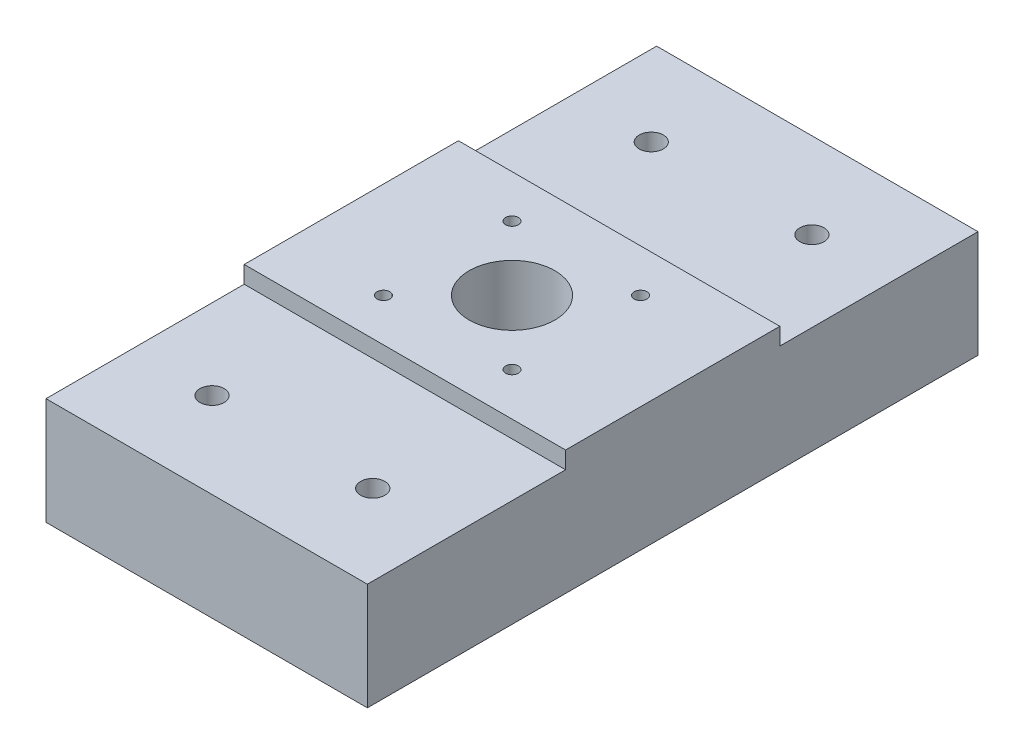
SolidWorks part; units mm, degrees
ref_plane "Front Plane" through (0, 0, 0) normal (0, 0, 1) x (1, 0, 0)
ref_plane "Top Plane" through (0, 0, 0) normal (0, 1, 0) x (1, 0, 0)
ref_plane "Right Plane" through (0, 0, 0) normal (1, 0, 0) x (0, 0, -1)
sketch "Sketch1" plane through (0, 0, 0) normal (0, 1, 0) x (1, 0, 0)
  line L0 (9, -22.5) -> (21, -22.5) construction
  line L1 (0, 0) -> (30, 0)
  line L2 (0, 0) -> (0, -57)
  line L3 (0, -57) -> (30, -57)
  line L4 (30, 0) -> (30, -57)
  line L5 (0, -18.5) -> (30, -18.5)
  line L6 (0, -18.5) -> (0, -38.5)
  line L7 (0, -38.5) -> (30, -38.5)
  line L8 (30, -18.5) -> (30, -38.5)
  line L9 (21, -22.5) -> (21, -34.5) construction
  line L10 (21, -34.5) -> (9, -34.5) construction
  line L11 (9, -34.5) -> (9, -22.5) construction
  circle A0 centre (15, -28.5) radius 4
  point P11 (15, 0)
  point P12 (22.5, -49)
  point P13 (9, -22.5)
  point P14 (21, -34.5)
  point P15 (9, -34.5)
  point P16 (7.5, -8)
  point P17 (22.5, -8)
  point P20 (8.5074, -34.6341)
  point P21 (7.5, -49)
  point P22 (15, -22.5)
  point P23 (21, -22.5)
  point P24 (21, -28.5)
  dimension "D3" = 8
  dimension "D1" = 57
  dimension "D2" = 30
  dimension "D4" = 10
  dimension "D5" = 20
  dimension "D6" = 15
  dimension "D7" = 7.5
  dimension "D8" = 18.5
  dimension "D9" = 8
  dimension "D10" = 8
  dimension "D11" = 12
extrude "Main_Body" add sketch "Sketch1" along normal blind 10 contours L7 L2 L3 L4 | L2 L7 L4 L5 A0 | L2 L5 L4 L1 region at (15, 0, 9.25) region at (15, 0, 18.8606) region at (15, 0, 47.75)
extrude "Boss-Extrude2" add sketch "Sketch1<3>" along normal blind 1.6 from surface contours L2 L7 L4 L5 A0 region at (15, 0, 18.8606) starting at face at (15, 10, 28.5)
sketch "Sketch1<3>" plane through (0, 0, 0) normal (0, 1, 0) x (1, 0, 0) same geometry as "Sketch1"
hole_wizard "#4-40 Tapped Hole1" positions "3DSketch1" profile "Sketch2" tap size "#4-40" standard "ANSI Inch"
sketch3d "3DSketch1"
  point P0 (7.5, 10, 8)
  point P2 (22.5, 10, 8)
  point P4 (7.5, 10, 49)
  point P6 (22.5, 10, 49)
  point P9 (0, 0, 0)
  point P11 (0, 0, 0)
  point P13 (0, 0, 0)
  point P15 (0, 0, 0)
  point P18 (0, 0, 0)
sketch "Sketch2" plane through (7.5, 10, 8) normal (1, 0, 0) x (0, 0, 1)
  line L0 (0, 0) -> (0, 8.2792)
  line L1 (0, 8.2792) -> (1.1303, 7.6)
  line L2 (1.1303, 7.6) -> (1.1303, 0)
  line L5 (1.1303, 0) -> (0, 0)
  line L10 (0, 8.2792) -> (-1.1303, 7.6) construction
  line L11 (0, -6.35) -> (0, 107.95) construction
  dimension "Tap Drill Dia." = 2.2606
  dimension "Tap Drill Depth" = 7.6
  dimension "Drill Angle" = 118
cosmetic thread "Hole Thread1" parameters "D1"=5.69, "D2"=2.8448
cosmetic thread "Hole Thread2" parameters "D1"=5.69, "D2"=2.8448
cosmetic thread "Hole Thread3" parameters "D1"=5.69, "D2"=2.8448
cosmetic thread "Hole Thread4" parameters "D1"=5.69, "D2"=2.8448
ref_plane "chip_example_plane" through (0, 11.6, 0) normal (0, 1, 0) x (1, 0, 0)
sketch "Chip_Example" plane through (0, 11.6, 0) normal (0, 1, 0) x (1, 0, 0)
  line L0 (0, 0) -> (30, 0) construction
  line L1 (10.5, -24) -> (19.5, -24)
  line L2 (10.5, -24) -> (10.5, -33)
  line L3 (10.5, -33) -> (19.5, -33)
  line L4 (19.5, -24) -> (19.5, -33)
  line L7 (30, -18.5) -> (0, -18.5) construction
  point P4 (15, -24)
  point P7 (15, 0)
  point P10 (19.5, -28.5)
  dimension "D1" = 9
  dimension "D2" = 10
hole_wizard "#0-80 Tapped Hole1" positions "3DSketch2" profile "Sketch4" tap size "#0-80" standard "ANSI Inch"
sketch3d "3DSketch2"
  point P0 (9, 0, 22.5)
  point P3 (21, 0, 22.5)
  point P6 (21, 0, 34.5)
  point P9 (9, 0, 34.5)
  point P13 (21, 11.6, 34.5)
  point P15 (21, 11.6, 22.5)
  point P17 (9, 11.6, 22.5)
  point P19 (9, 11.6, 34.5)
  point P22 (0, 0, 0)
  point P23 (0, 0, 0)
  point P24 (0, 0, 0)
  point P25 (0, 0, 0)
sketch "Sketch4" plane through (9, 11.6, 34.5) normal (1, 0, 0) x (0, 0, 1)
  line L0 (0, 0) -> (0, 4.3579)
  line L1 (0, 4.3579) -> (0.5956, 4)
  line L2 (0.5956, 4) -> (0.5956, 0)
  line L5 (0.5956, 0) -> (0, 0)
  line L10 (0, 4.3579) -> (-0.5956, 4) construction
  line L11 (0, -6.35) -> (0, 107.95) construction
  dimension "Tap Drill Dia." = 1.1913
  dimension "Tap Drill Depth" = 4
  dimension "Drill Angle" = 118
cosmetic thread "Hole Thread9" parameters "D1"=3.05, "D2"=1.524
cosmetic thread "Hole Thread10" parameters "D1"=3.05, "D2"=1.524
cosmetic thread "Hole Thread11" parameters "D1"=3.05, "D2"=1.524
cosmetic thread "Hole Thread12" parameters "D1"=3.05, "D2"=1.524
equation "\"D4@Sketch1\"=\"D5@Sketch1\"/2"
equation "\"D7@Sketch1\"=(\"D2@Sketch1\"-\"D6@Sketch1\")/2"
equation "\"PCB\"=1.6"
equation "\"D1@Boss-Extrude2\"=\"PCB\" + \"lift\""
equation "\"D8@Sketch1\"=(\"D1@Sketch1\"-\"D5@Sketch1\")/2"
equation "\"D9@Sketch1\"=\"D10@Sketch1\""
